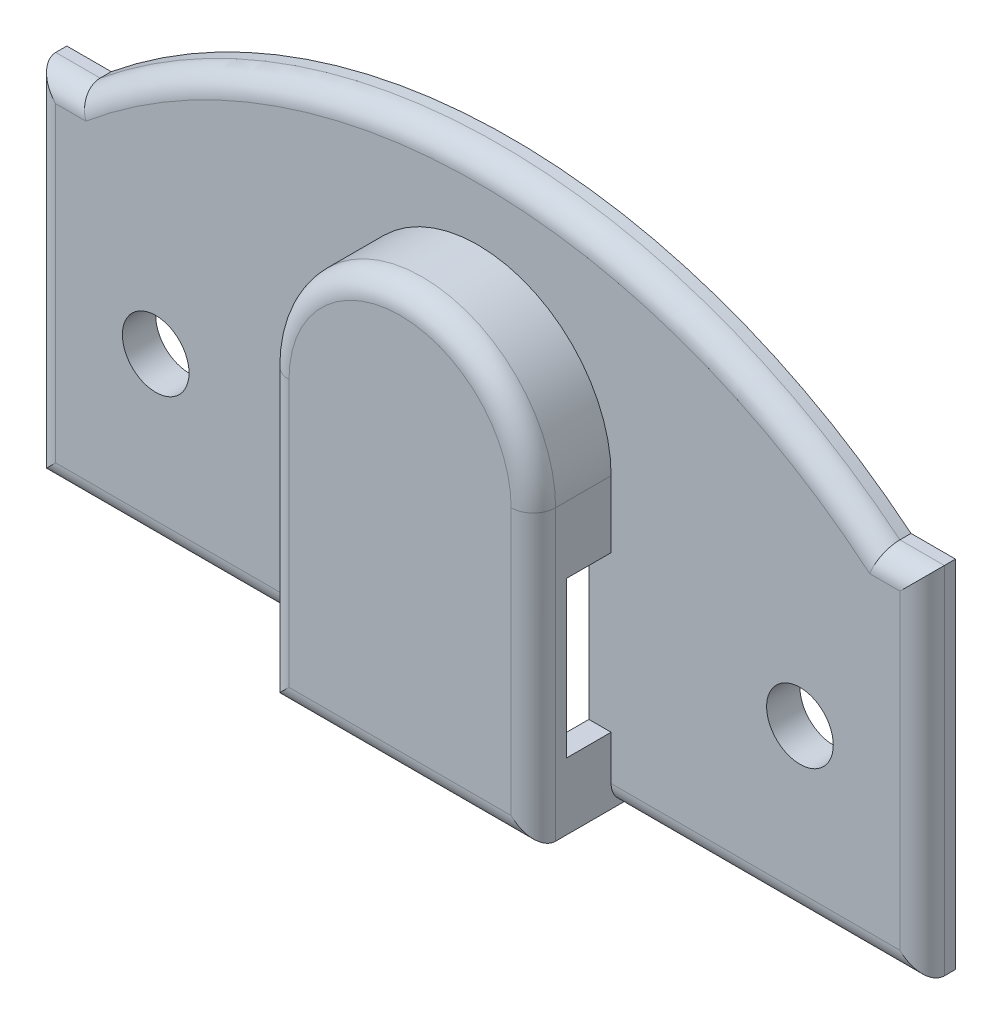
SolidWorks part; units mm, degrees
ref_plane "Front" through (0, 0, 0) normal (0, 0, 1) x (1, 0, 0)
ref_plane "Top" through (0, 0, 0) normal (0, 1, 0) x (1, 0, 0)
ref_plane "Right" through (0, 0, 0) normal (1, 0, 0) x (0, 0, -1)
sketch "Sketch1" plane through (0, 0, 0) normal (0, 0, 1) x (1, 0, 0)
  line L0 (0, 0) -> (20, 0)
  line L1 (55, 0) -> (-55, 0) construction
  line L2 (20, 0) -> (20, 16)
  line L4 (-20, 16) -> (-20, 0)
  line L5 (-20, 0) -> (0, 0)
  line L6 (-20, 16) -> (-18, 16)
  line L7 (20, 16) -> (18, 16)
  arc A0 (-18, 16) -> (18, 16) centre (0, -6.0731) cw
  dimension "D3" = 2
  dimension "D5" = 16
  dimension "D7" = 28.4819
  dimension "D1" = 20
  dimension "D2" = 20
  dimension "D4" = 2
  dimension "D6" = 16
extrude "Boss-Extrude1" add sketch "Sketch1" along normal blind 1.5
sketch "Sketch2" plane through (0, 0, 1.5) normal (0, 0, 1) x (1, 0, 0)
  line L1 (0.825, 0) -> (-0.825, 0) construction
  line L2 (6, 0) -> (6, 13)
  line L4 (-6, 0) -> (-6, 13)
  line L5 (-6, 0) -> (6, 0)
  arc A1 (-6, 13) -> (6, 13) centre (0, 13) cw
  dimension "D1" = 6
  dimension "D3" = 13
  dimension "D4" = 13
  dimension "D2" = 6
extrude "Boss-Extrude2" add sketch "Sketch2" along normal blind 3.5 contours A1 L2 L5 L4
sketch "Sketch3" plane through (0, 0, 0) normal (0, 0, -1) x (-1, 0, 0)
  line L0 (0, 0) -> (5, 0)
  line L1 (0.825, 0) -> (-0.825, 0) construction
  line L2 (5, 0) -> (5, 12)
  line L3 (0, 0) -> (-5, 0)
  line L4 (-5, 0) -> (-5, 12)
  arc A0 (-5, 12) -> (5, 12) centre (0, 12) cw
  dimension "D1" = 5
  dimension "D2" = 5
  dimension "D3" = 12
  dimension "D4" = 12
extrude "Cut-Extrude1" cut sketch "Sketch3" against normal blind 4 contours A0 L2 L0 L3 L4
sketch "Sketch4" plane through (-6, 0, 0) normal (-1, 0, 0) x (0, 0, 1)
  line L0 (1.5, 3) -> (3.5, 3)
  line L1 (1.5, 0) -> (1.5, 13) construction
  line L2 (3.5, 3) -> (3.5, 10)
  line L3 (3.5, 10) -> (1.5, 10)
  line L4 (1.5, 16) -> (1.5, 0) construction
  line L5 (1.5, 10) -> (1.5, 3)
  dimension "D1" = 2
  dimension "D2" = 7
  dimension "D3" = 3
extrude "Cut-Extrude2" cut sketch "Sketch4" against normal blind 12
fillet "Fillet1" radius 1 4 edges at (0, 19, 5) (6, 6.5, 5) (0, 0, 5) (-6, 6.5, 5)
fillet "Fillet4" radius 1 7 edges at (13, 0, 1.5) (20, 8, 1.5) (19, 16, 1.5) (-13, 0, 1.5) (0, 22.4089, 1.5) (-19, 16, 1.5) (-20, 8, 1.5)
sketch "Sketch5" plane through (0, 0, 1.5) normal (0, 0, 1) x (1, 0, 0)
  line L0 (-19, 1) -> (-6, 1) construction
  line L1 (0, -2.75) -> (0, 2.75) construction
  circle A0 centre (-14.4996, 7.5) radius 1.5
  circle A1 centre (14.4996, 7.5) radius 1.5
  point P2 (0, 0)
  dimension "D1" = 3
  dimension "D2" = 6.5
  dimension "D3" = 4.5004
extrude "Cut-Extrude3" cut sketch "Sketch5" against normal blind 12 contours A1 | A0 region at (14.4996, 7.5, 1.5)
